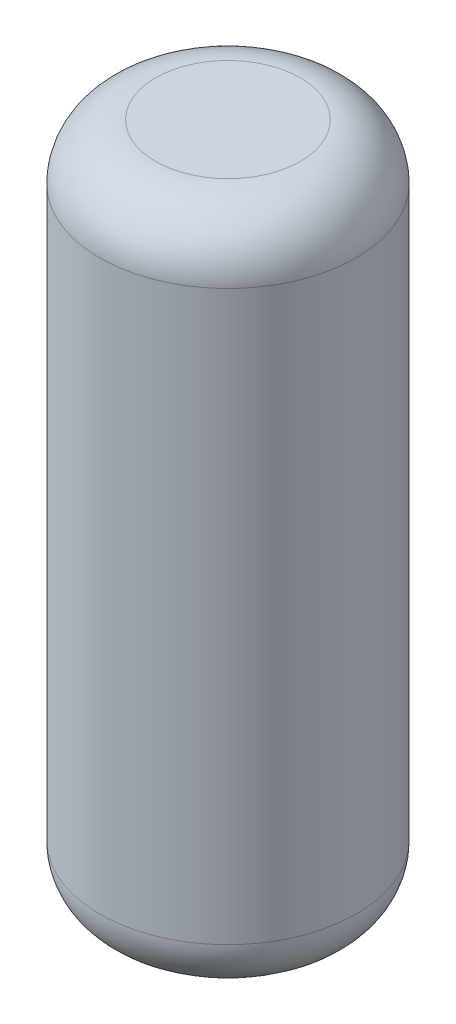
SolidWorks part; units mm, degrees
material "Thornel Mat VMA"
ref_plane "Front Plane" through (0, 0, 0) normal (0, 0, 1) x (1, 0, 0)
ref_plane "Top Plane" through (0, 0, 0) normal (0, 1, 0) x (1, 0, 0)
ref_plane "Right Plane" through (0, 0, 0) normal (1, 0, 0) x (0, 0, -1)
sketch "Sketch2" plane through (0, 0, 0) normal (0, 0, 1) x (1, 0, 0)
  line L0 (0, 232.41) -> (0, -232.41) construction
  line L1 (0, 232.41) -> (0, 156.21) construction
  line L2 (87.63, 156.21) -> (-87.63, 156.21) construction
  line L3 (0, -232.41) -> (0, -156.21) construction
  line L4 (-87.63, -156.21) -> (87.63, -156.21) construction
  line L5 (0, -232.41) -> (49.53, -232.41)
  line L6 (87.63, -194.31) -> (87.63, -156.21)
  line L7 (0, 232.41) -> (49.53, 232.41)
  line L8 (87.63, 194.31) -> (87.63, 156.21)
  line L9 (87.63, 156.21) -> (87.63, -156.21)
  line L10 (0, -232.41) -> (0, 232.41)
  arc A0 (49.53, -232.41) -> (87.63, -194.31) centre (49.53, -194.31) ccw
  arc A1 (49.53, 232.41) -> (87.63, 194.31) centre (49.53, 194.31) cw
  point P4 (0, 0)
  point P8 (0, 156.21)
  point P12 (0, -156.21)
  dimension "D6" = 38.1
  dimension "D1" = 464.82
  dimension "D2" = 76.2
  dimension "D3" = 175.26
  dimension "D4" = 76.2
  dimension "D5" = 175.26
revolve "Revolve1" add sketch "Sketch2" angle 360 about L10
sketch "Sketch3" plane through (0, -232.41, 0) normal (0, -1, 0) x (-1, 0, 0)
  circle A0 centre (0, 0) radius 12.7
  dimension "D1" = 25.4
extrude "Boss-Extrude1" add sketch "Sketch3" along normal blind 19.05
shell "Shell1" thickness 2.54 removed face at (0, -251.46, -12.7)
sketch "Sketch5" plane through (0, -251.46, 0) normal (0, -1, 0) x (1, 0, 0)
  circle A0 centre (0, 0) radius 7.9375
  dimension "D1" = 15.875
sketch "Sketch6" plane through (0, -251.46, 0) normal (0, -1, 0) x (-1, 0, 0)
  circle A0 centre (0, 0) radius 12.7
  dimension "D1" = 25.4
extrude "Boss-Extrude2" add sketch "Sketch6" against normal blind 25.4 from offset 6.35
sketch "Sketch7" plane through (0, -257.81, 0) normal (0, -1, 0) x (1, 0, 0)
  circle A0 centre (0, 0) radius 7.9375
  dimension "D1" = 15.875
extrude "Cut-Extrude3" cut sketch "Sketch7" against normal blind 25.4
